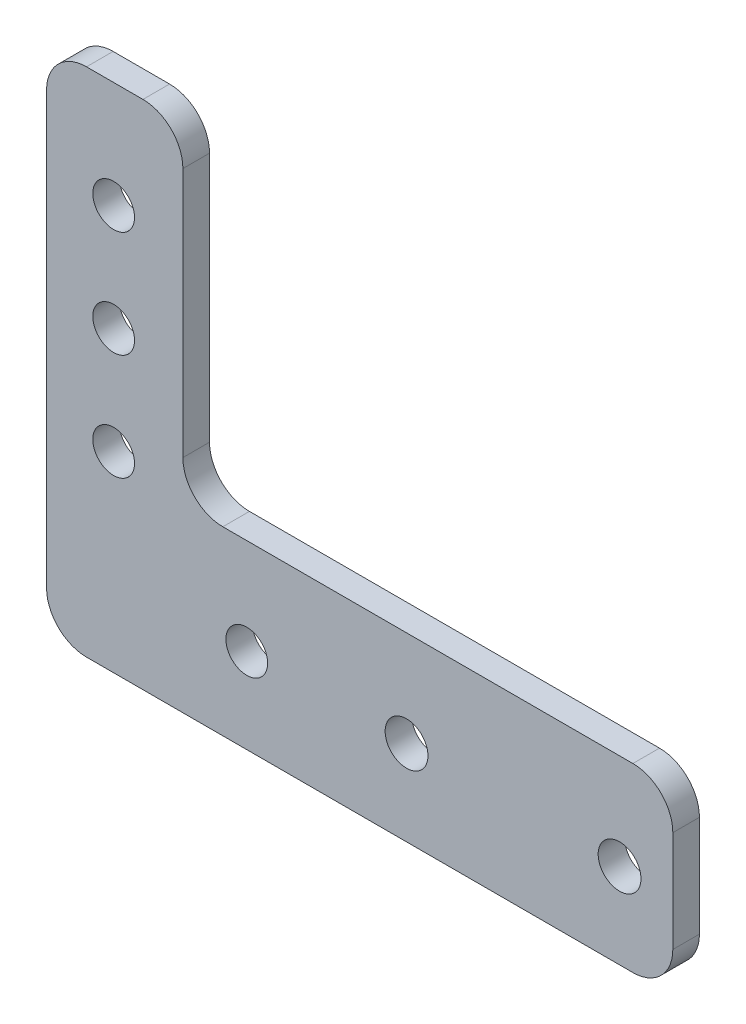
SolidWorks part; units mm, degrees
material "6061-T6 (SS)"
ref_plane "Front Plane" through (0, 0, 0) normal (0, 0, 1) x (1, 0, 0)
ref_plane "Top Plane" through (0, 0, 0) normal (0, 1, 0) x (1, 0, 0)
ref_plane "Right Plane" through (0, 0, 0) normal (1, 0, 0) x (0, 0, -1)
sketch "Sketch1" plane through (0, 0, 0) normal (0, 0, 1) x (1, 0, 0)
  line L1 (-41.275, -31.75) -> (41.275, -31.75)
  line L2 (-41.275, -31.75) -> (-41.275, 31.75)
  line L3 (-41.275, 31.75) -> (41.275, 31.75)
  line L4 (41.275, -31.75) -> (41.275, 31.75)
  line L5 (-41.275, -31.75) -> (41.275, 31.75) construction
  line L6 (-41.275, 31.75) -> (41.275, -31.75) construction
  line L7 (41.275, 31.75) -> (-17.145, 31.75)
  line L8 (41.275, 31.75) -> (41.275, -7.62)
  line L9 (41.275, -7.62) -> (-17.145, -7.62)
  line L10 (-17.145, 31.75) -> (-17.145, -7.62)
  line L11 (-41.275, -31.75) -> (-33.401, -31.75)
  line L12 (-41.275, -31.75) -> (-41.275, 31.75)
  line L13 (-41.275, 31.75) -> (-33.401, 31.75)
  line L14 (-33.401, -31.75) -> (-33.401, 31.75)
  line L15 (-33.401, -31.75) -> (41.275, -31.75)
  line L16 (-33.401, -31.75) -> (-33.401, -29.21)
  line L17 (-33.401, -29.21) -> (41.275, -29.21)
  line L18 (41.275, -31.75) -> (41.275, -29.21)
  circle A0 centre (-25.4, -19.05) radius 2.4892
  circle A1 centre (-25.4, -6.35) radius 2.4892
  circle A2 centre (-25.4, 6.35) radius 2.4892
  circle A3 centre (-25.4, 19.05) radius 2.4892
  circle A4 centre (-9.525, -19.05) radius 2.4892
  circle A5 centre (9.525, -19.05) radius 2.5527
  circle A7 centre (34.925, -19.05) radius 2.5527
  point P0 (0, 0)
  dimension "D7" = 4.9784
  dimension "D18" = 5.1054
  dimension "D15" = 50.8
  dimension "D14" = 15.875
  dimension "D1" = 82.55
  dimension "D2" = 63.5
  dimension "D3" = 24.13
  dimension "D4" = 24.13
  dimension "D5" = 7.874
  dimension "D6" = 63.5
  dimension "D8" = 15.875
  dimension "D9" = 12.7
  dimension "D10" = 12.7
  dimension "D11" = 12.7
  dimension "D12" = 12.7
  dimension "D13" = 25.4
  dimension "D16" = 2.54
extrude "Boss-Extrude1" add sketch "Sketch1" along normal blind 3.175 contours L14 L17 L4 L9 L10 L3 A5 A4 A3 A2 A1 A0 | A0 region at (-4.0559, -9.8474, 0) region at (-25.4, -19.05, 0)
fillet "Fillet1" radius 4.7625 6 edges at (-33.401, 31.75, 1.5875) (-17.145, 31.75, 1.5875) (-17.145, -7.62, 1.5875) (41.275, -7.62, 1.5875) (41.275, -29.21, 1.5875) (-33.401, -29.21, 1.5875)
